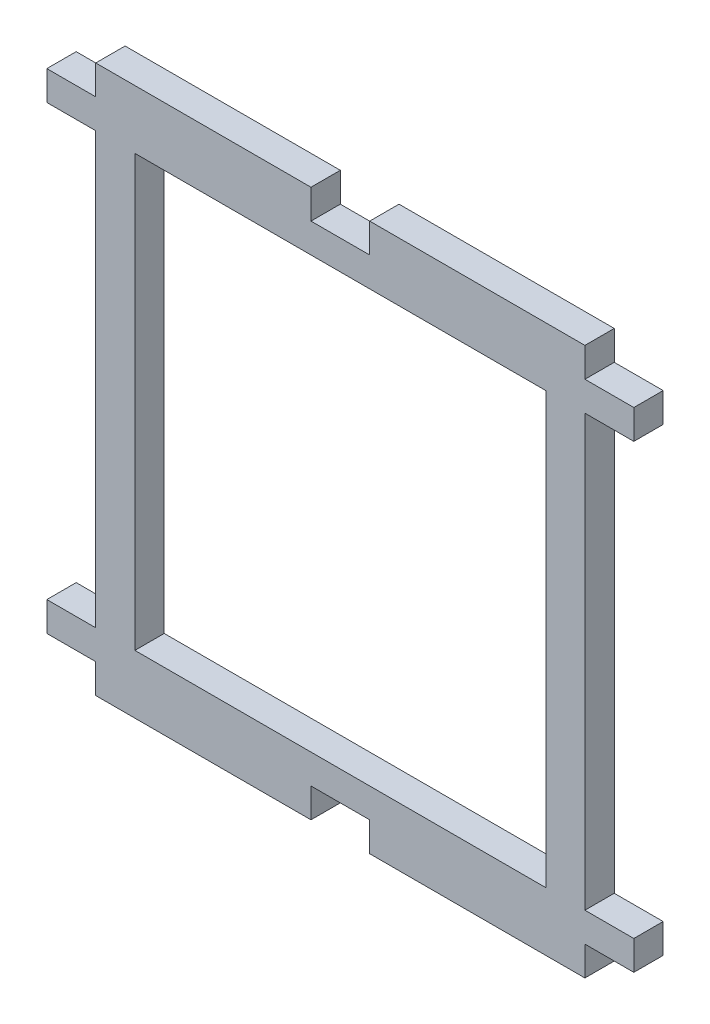
SolidWorks part; units mm, degrees
material "Custom Plastic"
ref_plane "Front Plane" through (0, 0, 0) normal (0, 0, 1) x (1, 0, 0)
ref_plane "Top Plane" through (0, 0, 0) normal (0, 1, 0) x (1, 0, 0)
ref_plane "Right Plane" through (0, 0, 0) normal (1, 0, 0) x (0, 0, -1)
sketch "Sketch1" plane through (0, 0, 0) normal (0, 0, 1) x (1, 0, 0)
  line L0 (-41.2824, 35.9958) -> (-36.2824, 35.9958)
  line L1 (-36.2824, 35.9958) -> (-36.2824, -8.0042)
  line L2 (-36.2824, -8.0042) -> (-41.2824, -8.0042)
  line L3 (-41.2824, -8.0042) -> (-41.2824, -11.0042)
  line L4 (-41.2824, -11.0042) -> (-36.2824, -11.0042)
  line L5 (-36.2824, -11.0042) -> (-36.2824, -14.0042)
  line L6 (-36.2824, -14.0042) -> (-14.2824, -14.0042)
  line L7 (-14.2824, -14.0042) -> (-14.2824, -11.0042)
  line L8 (-14.2824, -11.0042) -> (-8.2824, -11.0042)
  line L9 (-8.2824, -11.0042) -> (-8.2824, -14.0042)
  line L10 (-8.2824, -14.0042) -> (13.7176, -14.0042)
  line L11 (13.7176, -14.0042) -> (13.7176, -11.0042)
  line L12 (13.7176, -11.0042) -> (18.7176, -11.0042)
  line L13 (18.7176, -11.0042) -> (18.7176, -8.0042)
  line L14 (18.7176, -8.0042) -> (13.7176, -8.0042)
  line L15 (13.7176, -8.0042) -> (13.7176, 35.9958)
  line L16 (13.7176, 35.9958) -> (18.7176, 35.9958)
  line L17 (18.7176, 35.9958) -> (18.7176, 38.9958)
  line L18 (18.7176, 38.9958) -> (13.7176, 38.9958)
  line L19 (13.7176, 38.9958) -> (13.7176, 41.9958)
  line L20 (13.7176, 41.9958) -> (-8.2824, 41.9958)
  line L21 (-8.2824, 41.9958) -> (-8.2824, 38.9958)
  line L22 (-8.2824, 38.9958) -> (-14.2824, 38.9958)
  line L23 (-14.2824, 38.9958) -> (-14.2824, 41.9958)
  line L24 (-14.2824, 41.9958) -> (-36.2824, 41.9958)
  line L25 (-36.2824, 41.9958) -> (-36.2824, 38.9958)
  line L26 (-36.2824, 38.9958) -> (-41.2824, 38.9958)
  line L27 (-41.2824, 38.9958) -> (-41.2824, 35.9958)
  line L28 (-36.2824, -8.0042) -> (13.7176, -8.0042) construction
  line L29 (-36.2824, 35.9958) -> (13.7176, 35.9958) construction
  line L30 (-32.2824, -8.0042) -> (-32.2824, 35.9958)
  line L31 (-32.2824, 35.9958) -> (9.7176, 35.9958)
  line L33 (9.7176, -8.0042) -> (-32.2824, -8.0042)
  line L36 (9.7176, 35.9958) -> (9.7176, -8.0042)
  point P30 (28.7183, -7.4401)
  point P32 (28.8487, 35.9958)
  dimension "D1" = 50
  dimension "D2" = 3
  dimension "D3" = 3
  dimension "D4" = 22
  dimension "D5" = 4
  dimension "D6" = 6
  dimension "D7" = 5
  dimension "D9" = 4
extrude "Boss-Extrude1" add sketch "Sketch1" along normal blind 3
